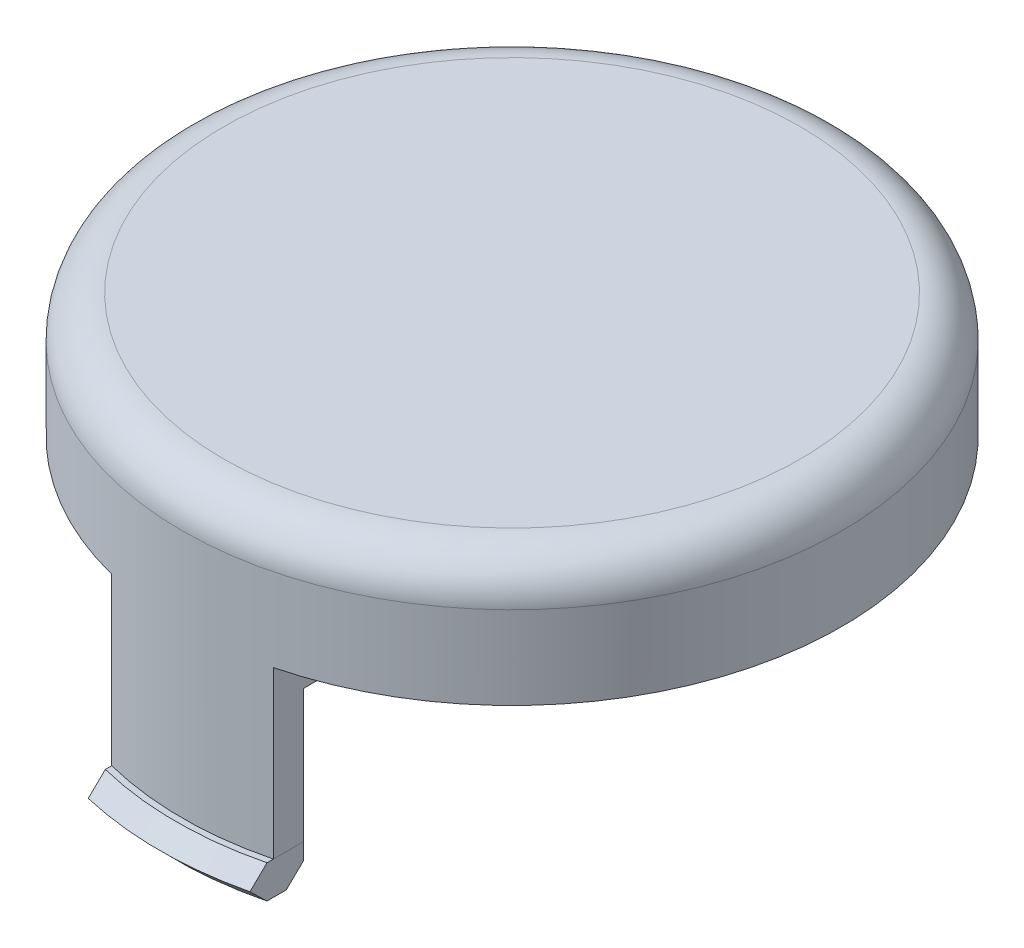
SolidWorks part; units mm, degrees
ref_plane "前视基准面" through (0, 0, 0) normal (0, 0, 1) x (1, 0, 0)
ref_plane "上视基准面" through (0, 0, 0) normal (0, 1, 0) x (1, 0, 0)
ref_plane "右视基准面" through (0, 0, 0) normal (1, 0, 0) x (0, 0, -1)
sketch "草图2" plane through (0, 0, 0) normal (0, 1, 0) x (1, 0, 0)
  circle A0 centre (0, 0) radius 7.95
  dimension "D1" = 15.9
extrude "凸台-拉伸1" add sketch "草图2" along normal blind 5
sketch "草图4" plane through (0, 0, 0) normal (0, -1, 0) x (1, 0, 0)
  circle A2 centre (0, 0) radius 8.5
  dimension "D1" = 17
extrude "凸台-拉伸2" add sketch "草图4" along normal blind 0.8 separate body
sketch "草图3" plane through (0, -0.8, 0) normal (0, -1, 0) x (1, 0, 0)
  circle A0 centre (0, 0) radius 7.25
  dimension "D1" = 14.5
extrude "切除-拉伸2" cut sketch "草图3" against normal blind 4
chamfer "倒角2" distance 0.4 angle 45 3 edges at (0, -0.8, -7.25) (0, -0.8, -8.5) (0, 0, -8.5)
sketch "草图5" plane through (0, 0, 0) normal (0, 0, 1) x (1, 0, 0)
  line L0 (-7.95, 5) -> (-7.95, 0) construction
  line L1 (-1.95, 4) -> (-7.95, 4)
  line L2 (-1.95, 4) -> (-1.95, -4)
  line L3 (-1.95, -4) -> (-7.95, -4)
  line L4 (-7.95, 4) -> (-7.95, -4)
  line L6 (1.95, 4) -> (7.95, 4)
  line L7 (1.95, 4) -> (1.95, -4)
  line L8 (1.95, -4) -> (7.95, -4)
  line L9 (7.95, 4) -> (7.95, -4)
  line L11 (7.95, 0) -> (7.95, 5) construction
  line L12 (7.95, 5) -> (-7.95, 5) construction
  dimension "D1" = 6
  dimension "D2" = 6
  dimension "D3" = 8
  dimension "D4" = 1
extrude "切除-拉伸3" cut sketch "草图5" against normal through all and the other way through all
sketch "草图6" plane through (0, 5, 0) normal (0, 1, 0) x (1, 0, 0)
  circle A1 centre (0, 0) radius 7.95
  circle A2 centre (0, 0) radius 7.95
  dimension "D1" = 0
extrude "凸台-拉伸3" add sketch "草图6" along normal blind 2
fillet "圆角1" radius 1 1 edges at (0, 7, 7.95)
sketch "草图7" plane through (0, 3.2, 0) normal (0, -1, 0) x (1, 0, 0)
  circle A0 centre (0, 0) radius 6.5
  dimension "D1" = 13
extrude "切除-拉伸4" cut sketch "草图7" against normal blind 1.5
sketch "草图9" plane through (0, 0, 0) normal (0, 0, 1) x (1, 0, 0)
  line L1 (-9.148, 0.757) -> (-7.1332, 0.757)
  line L2 (-9.148, 0.757) -> (-9.148, -1.5563)
  line L3 (-9.148, -1.5563) -> (-7.1332, -1.5563)
  line L4 (-7.1332, 0.757) -> (-7.1332, -1.5563)
  line L5 (6.871, 0.757) -> (8.8138, 0.757)
  line L6 (6.871, 0.757) -> (6.871, -2.1388)
  line L7 (6.871, -2.1388) -> (8.8138, -2.1388)
  line L8 (8.8138, 0.757) -> (8.8138, -2.1388)
extrude "切除-拉伸8" cut sketch "草图9" against normal through all and the other way through all
